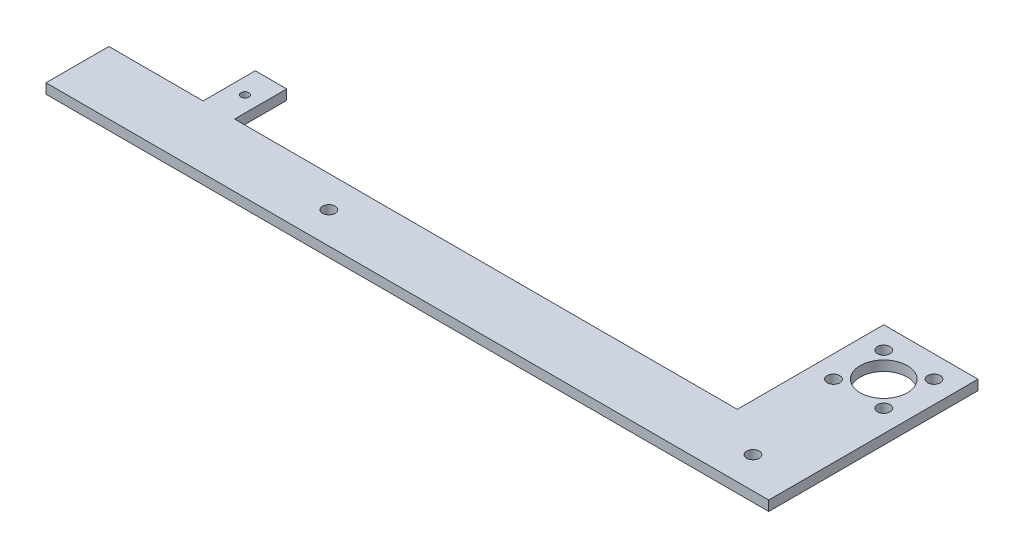
SolidWorks part; units mm, degrees
ref_plane "Front" through (0, 0, 0) normal (0, 0, 1) x (1, 0, 0)
ref_plane "Top" through (0, 0, 0) normal (0, 1, 0) x (1, 0, 0)
ref_plane "Right" through (0, 0, 0) normal (1, 0, 0) x (0, 0, -1)
sketch "Sketch1" plane through (0, 0, 0) normal (0, 1, 0) x (1, 0, 0)
  line L0 (190, -36.6) -> (190, 0)
  line L3 (0, -36.6) -> (190, -36.6)
  line L5 (190, -26.6) -> (0, -26.6)
  line L6 (190, -26.6) -> (175, -26.6)
  line L7 (175, -26.6) -> (40, -26.6)
  line L8 (0, -16.6) -> (160, -16.6)
  line L9 (160, 3.4) -> (160, -16.6)
  line L10 (190, 0) -> (190, 30)
  line L11 (190, 30) -> (160, 30)
  line L12 (160, 30) -> (160, 3.4)
  line L13 (0, -16.6) -> (0, 0)
  line L14 (175, 15) -> (175, 23)
  line L15 (175, 23) -> (183, 23)
  line L16 (183, 23) -> (183, 7)
  line L17 (183, 7) -> (167, 7)
  line L18 (167, 7) -> (167, 23)
  line L19 (167, 23) -> (175, 23)
  line L20 (0, -36.6) -> (-10, -36.6)
  line L21 (-10, 0) -> (-10, -16.6)
  line L22 (-10, 0) -> (0, 0)
  line L23 (0, -16.6) -> (-10, 0)
  line L24 (-10, -16.6) -> (-40, -16.6)
  line L25 (-40, -16.6) -> (-40, -53.6)
  line L26 (-40, -53.6) -> (-30, -53.6)
  line L27 (-30, -53.6) -> (-30, -36.6)
  line L28 (-30, -36.6) -> (-10, -36.6)
  line L29 (-30, -36.6) -> (-40, -53.6)
  line L30 (-30, -36.6) -> (-40, -36.6)
  circle A0 centre (40, -26.6) radius 2
  circle A1 centre (175, -26.6) radius 2
  circle A2 centre (183, 7) radius 2
  circle A3 centre (167, 7) radius 2
  circle A4 centre (183, 23) radius 2
  circle A5 centre (167, 23) radius 2
  circle A6 centre (175, 15) radius 7.5
  circle A7 centre (-5, -8.3) radius 1.25
  circle A9 centre (-35, -45.1) radius 1.5
  dimension "D5" = 160
  dimension "D11" = 10
  dimension "D12" = 30
  dimension "D15" = 15
  dimension "D2" = 190
  dimension "D3" = 15
  dimension "D4" = 135
  dimension "D6" = 30
  dimension "D7" = 8
  dimension "D8" = 8
  dimension "D9" = 8
  dimension "D10" = 16
  dimension "D13" = 37
  dimension "D14" = 10
  dimension "D16" = 20
  dimension "D17" = 16.6
extrude "Boss-Extrude1" add sketch "Sketch1" along normal blind 3.175 contours A7 L23 L13 L22 | A6 L19 A5 L18 A3 L17 A2 L16 A4 L15 | A7 L23 L21 L24 L25 L30 L28 L20 L3 L0 A1 A0 L10 L11 L12 L9 L8 A5 L19 L15 A4 L16 A2 L17 A3 L18 region at (92.8885, 0, 20.4225) region at (-3.2964, 0, 5.4574) region at (178, 0, -22.7737)
